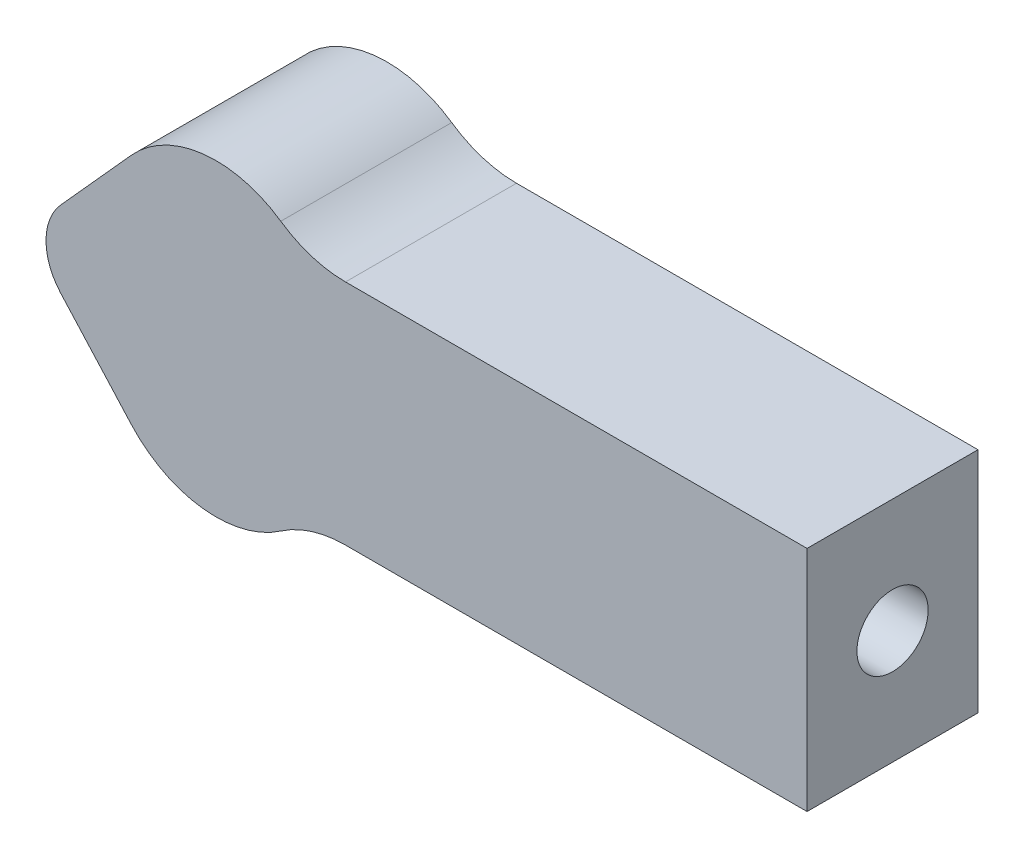
SolidWorks part; units mm, degrees
material "6061-T6 (SS)"
ref_plane "Front Plane" through (0, 0, 0) normal (0, 0, 1) x (1, 0, 0)
ref_plane "Top Plane" through (0, 0, 0) normal (0, 1, 0) x (1, 0, 0)
ref_plane "Right Plane" through (0, 0, 0) normal (1, 0, 0) x (0, 0, -1)
sketch "Sketch1" plane through (0, 0, 0) normal (0, 0, 1) x (1, 0, 0)
  line L0 (-3.05, 4) -> (-6.05, 0.6693)
  line L5 (-4.1825, -2.7426) -> (-3.05, -2) construction
  line L6 (-4.1825, 2.7426) -> (-3.05, 2) construction
  line L7 (-6.05, 0.6693) -> (-3.0711, -2.0138) construction
  line L8 (-6.05, -0.6693) -> (-3.05, -4)
  line L9 (-6.05, -0.6693) -> (-3.0711, 2.0138) construction
  line L10 (7.05, 2) -> (7.05, -2)
  line L15 (-3.05, 2) -> (-3.05, 4)
  line L16 (3.05, -2) -> (-3.05, -2)
  line L17 (-3.05, -2) -> (-3.05, -4)
  line L19 (3.05, 2) -> (-3.05, 2)
  line L21 (3.05, -2) -> (-3.05, 2) construction
  line L22 (3.05, 2) -> (-3.05, -2) construction
  line L23 (3.05, 2) -> (7.05, 2)
  line L25 (3.05, -2) -> (7.05, -2)
  arc A0 (-6.05, 0.6693) -> (-6.05, -0.6693) centre (-5.307, 0) ccw
  point P0 (0, 0)
  point P1 (0, 0)
  dimension "D6" = 4
  dimension "D4" = 1
  dimension "D1" = 6.1
  dimension "D2" = 4
  dimension "D3" = 3
  dimension "D5" = 2
  dimension "D7" = 6.1
extrude "Boss-Extrude1" add sketch "Sketch1" along normal blind 3 contours L8 L0 region at (0.3772, 0, 0)
fillet "Fillet2" radius 2 2 edges at (-3.05, -2, 1.5) (-3.05, 2, 1.5)
fillet "Fillet3" radius 2 2 edges at (-3.05, -4, 1.5) (-3.05, 4, 1.5)
sketch "Sketch2" plane through (7.05, 0, 0) normal (1, 0, 0) x (0, 0, -1)
  line L0 (-3, -2) -> (0, -2) construction
  point P0 (-1.5, 0)
  point P6 (-1.5, -2)
hole_wizard "M1.6 Tapped Hole1" positions "Sketch3" profile "Sketch4" tap size "M1.6" standard "ISO"
sketch "Sketch3" plane through (7.05, 0, 0) normal (1, 0, 0) x (0, 0, -1)
  point P0 (-1.5, 0)
sketch "Sketch4" plane through (7.05, 0, 1.5) normal (0, 1, 0) x (0, 0, -1)
  line L0 (0, 0) -> (0, 3.3755)
  line L1 (0, 3.3755) -> (0.625, 3)
  line L2 (0.625, 3) -> (0.625, 0)
  line L5 (0.625, 0) -> (0, 0)
  line L10 (0, 3.3755) -> (-0.625, 3) construction
  line L11 (0, -6.35) -> (0, 107.95) construction
  dimension "Tap Drill Dia." = 1.25
  dimension "Tap Drill Depth" = 3
  dimension "Drill Angle" = 118
cosmetic thread "Hole Thread1" parameters "D1"=3, "D2"=1.6
